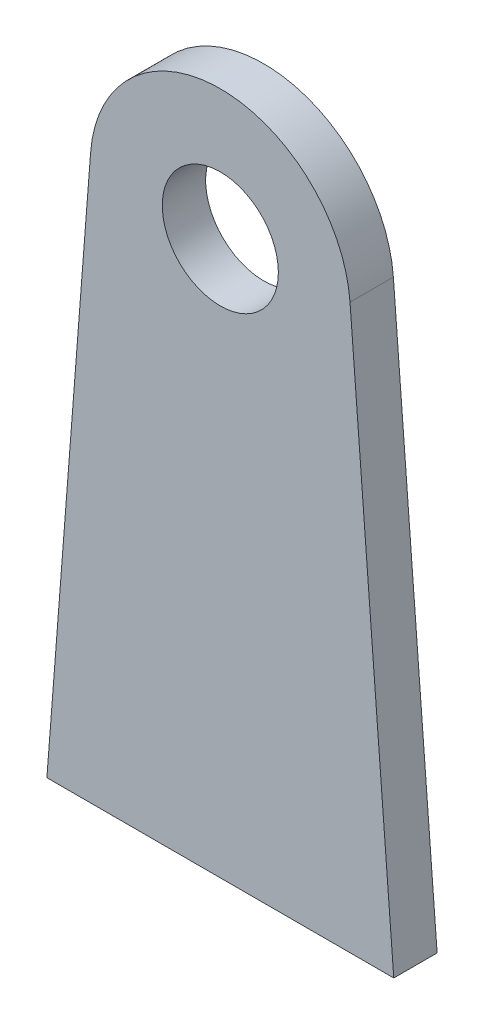
SolidWorks part; units mm, degrees
ref_plane "Front Plane" through (0, 0, 0) normal (0, 0, 1) x (1, 0, 0)
ref_plane "Top Plane" through (0, 0, 0) normal (0, 1, 0) x (1, 0, 0)
ref_plane "Right Plane" through (0, 0, 0) normal (1, 0, 0) x (0, 0, -1)
sketch "Sketch1" plane through (0, 0, 0) normal (0, 0, 1) x (1, 0, 0)
  line L0 (0, 0) -> (0, -35.9042) construction
  line L1 (-12.7, -35.9042) -> (12.7, -35.9042)
  line L2 (12.7, -35.9042) -> (9.4888, 0.8295)
  line L3 (-12.7, -35.9042) -> (-9.4888, 0.8295)
  line L6 (2.4398, -45.0067) -> (-67.8292, 217.1568) construction
  circle A0 centre (0, 0) radius 4.25
  circle A1 centre (0, 0) radius 9.525
  point P9 (0, 0)
  dimension "D2" = 8.5
  dimension "D3" = 19.05
  dimension "D1" = 12.7
extrude "Boss-Extrude1" [suppressed] add sketch "Sketch1" along normal blind 3.175 contours A0 A1 | L0 A1 L3 L1 | A1 L0 L1 L2
sketch "Sketch2" plane through (0, 0, 0) normal (0, 0, 1) x (1, 0, 0)
  line L0 (1.1534, 0.3092) -> (1.1534, -40.2074) construction
  line L1 (-11.5466, -40.2074) -> (13.8534, -40.2074)
  line L2 (13.8534, -40.2074) -> (10.6498, 1.0466)
  line L3 (-11.5466, -40.2074) -> (-8.343, 1.0466)
  line L5 (2.4398, -45.0067) -> (-67.8292, 217.1568) construction
  circle A0 centre (1.1534, 0.3092) radius 4.25
  circle A1 centre (1.1534, 0.3092) radius 9.525
  point P9 (0, -45.1289)
  dimension "D2" = 8.5
  dimension "D3" = 19.05
  dimension "D1" = 12.7
extrude "Boss-Extrude2" add sketch "Sketch2" along normal blind 3.175 contours A0 A1 | L0 A1 L3 L1 | A1 L0 L1 L2 region at (-5.6399, -5.9771, 0) region at (7.0464, -24.1268, 0) region at (-4.7396, -24.1268, 0)
